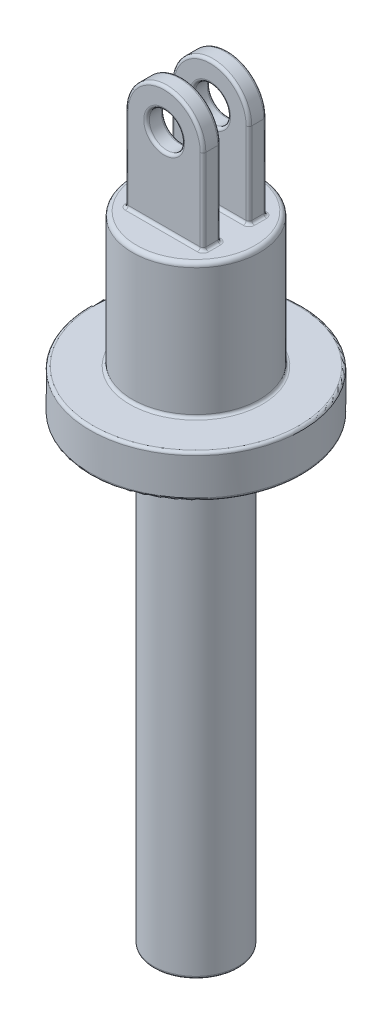
SolidWorks part; units mm, degrees
ref_plane "Front Plane" through (0, 0, 0) normal (0, 0, 1) x (1, 0, 0)
ref_plane "Top Plane" through (0, 0, 0) normal (0, 1, 0) x (1, 0, 0)
ref_plane "Right Plane" through (0, 0, 0) normal (1, 0, 0) x (0, 0, -1)
sketch "Sketch1" plane through (0, 0, 0) normal (0, 0, 1) x (1, 0, 0)
  line L0 (0, 0) -> (0, 45)
  line L1 (0, 45) -> (-4.5, 45)
  line L2 (-4.5, 45) -> (-4.5, 35.5)
  line L3 (-4.5, 35.5) -> (-7.5, 35.5)
  line L4 (-7.5, 35.5) -> (-7.5, 32.5)
  line L5 (-7.5, 32.5) -> (-3, 32.5)
  line L6 (-3, 32.5) -> (-3, 0)
  line L7 (-3, 0) -> (0, 0)
  dimension "D1" = 45
  dimension "D2" = 32.5
  dimension "D3" = 3
  dimension "D4" = 4.5
  dimension "D5" = 3
  dimension "D6" = 3
revolve "Revolve1" add sketch "Sketch1" angle 360 about L0
sketch "Sketch2" plane through (0, 0, 0) normal (0, 0, 1) x (1, 0, 0)
  line L0 (4.5, 45) -> (-4.5, 45) construction
  line L1 (2.75, 51) -> (2.75, 45)
  line L2 (2.75, 45) -> (-2.75, 45)
  line L3 (-2.75, 45) -> (-2.75, 51)
  circle A0 centre (0, 51) radius 1.25
  arc A1 (2.75, 51) -> (-2.75, 51) centre (0, 51) ccw
  circle A2 centre (0, 51) radius 2.75 construction
  dimension "D1" = 2.5
  dimension "D2" = 6
  dimension "D3" = 1.5
extrude "Boss-Extrude2" add sketch "Sketch2" along normal blind 1.25 from offset 1
extrude "Boss-Extrude3" add sketch "Sketch2<2>" against normal blind 1.25 from offset 1 offset against normal yes
sketch "Sketch2<2>" plane through (0, 0, 0) normal (0, 0, 1) x (1, 0, 0) same geometry as "Sketch2"
fillet "Fillet1" radius 0.3 1 edges at (0, 45, -4.5)
sketch "Sketch4" plane through (0, 0, 0) normal (0, -1, 0) x (1, 0, 0)
  circle A0 centre (0, 0) radius 1.25
  dimension "D1" = 2.5
extrude "Cut-Extrude1" cut sketch "Sketch4" against normal blind 32.5
fillet "Fillet2" radius 0.2 24 edges at (1.25, 51, 1) (1.25, 51, 2.25) (0, 53.75, 1) (-2.75, 48, 1) (0, 45, 1) (0, 53.75, 2.25) (-2.75, 48, 2.25) (0, 45, 2.25) (2.75, 48, 2.25) (2.75, 45, 1.625) (-2.75, 45, 1.625) (2.75, 48, 1) (1.25, 51, -1) (1.25, 51, -2.25) (0, 53.75, -1) (-2.75, 48, -1) (0, 45, -1) (2.75, 48, -1) (0, 53.75, -2.25) (-2.75, 48, -2.25) (0, 45, -2.25) (-2.75, 45, -1.625) (2.75, 45, -1.625) (2.75, 48, -2.25)
fillet "Fillet3" radius 0.2 6 edges at (0, 0, -3) (0, 0, -1.25) (0, 32.5, -3) (0, 32.5, -7.5) (0, 35.5, -4.5) (0, 35.5, -7.5)
sketch "Sketch6" plane through (0, 32.5, 0) normal (0, -1, 0) x (1, 0, 0)
  circle A0 centre (0, 0) radius 6
  dimension "D1" = 12
